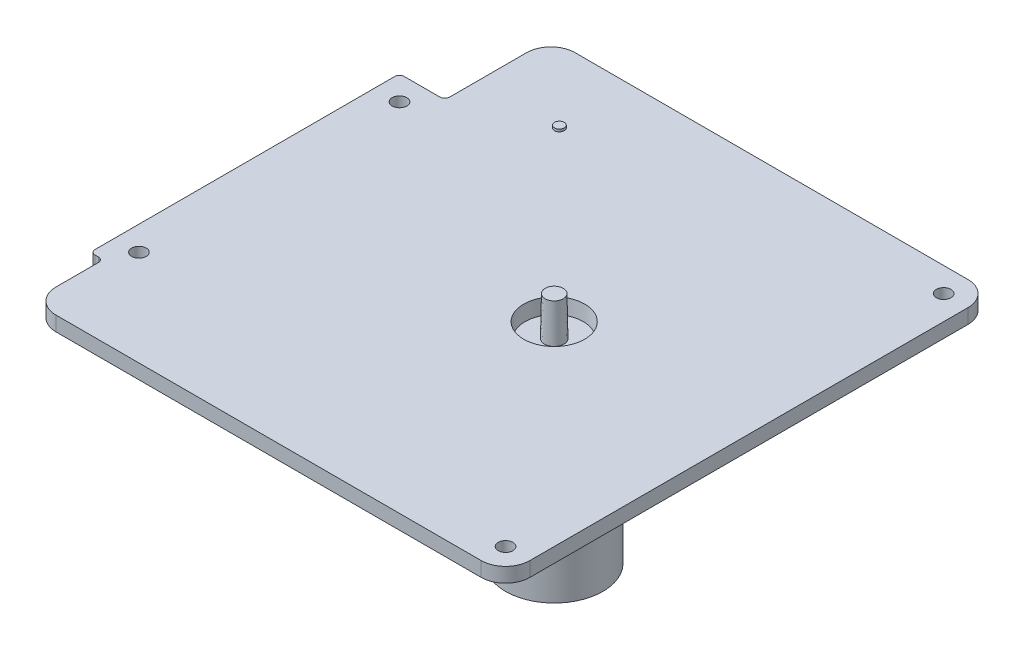
SolidWorks part; units mm, degrees
ref_plane "Front Plane" through (0, 0, 0) normal (0, 0, 1) x (1, 0, 0)
ref_plane "Top Plane" through (0, 0, 0) normal (0, 1, 0) x (1, 0, 0)
ref_plane "Right Plane" through (0, 0, 0) normal (1, 0, 0) x (0, 0, -1)
ref_plane "Plane1" through (0, 23, 0) normal (0, 1, 0) x (1, 0, 0)
sketch "Sketch1" plane through (0, 23, 0) normal (0, 1, 0) x (1, 0, 0)
  line L0 (98.3054, 50) -> (98.3054, 28.2195)
  line L1 (189, 50) -> (98.3054, 50)
  line L2 (189, 50) -> (189, -50)
  line L3 (189, -50) -> (97.6502, -50)
  line L5 (98.3054, 28.2195) -> (89, 28.2195)
  line L6 (89, 28.2195) -> (89, -35.308)
  line L7 (89, -35.308) -> (91.6598, -35.308)
  line L8 (91.6598, -35.308) -> (91.6598, -50)
  line L9 (91.6598, -50) -> (97.6502, -50)
  line L10 (94.8054, 33.2195) -> (98.3054, 33.2195) construction
  line L11 (184, 45) -> (184, 50) construction
  line L12 (93.3054, 31.7195) -> (93.3054, 28.2195) construction
  line L13 (99.4745, -35.308) -> (86.1225, -35.308) construction
  line L14 (88.1598, -40.308) -> (91.6598, -40.308) construction
  line L15 (86.6598, -38.808) -> (86.6598, -35.308) construction
  line L16 (189, 0) -> (190, 0) construction
  line L17 (190, -60) -> (190, 60) construction
  line L18 (105.0183, -40) -> (185.0183, -40) construction
  line L19 (105.0183, -40) -> (105.0183, 40) construction
  line L20 (105.0183, 40) -> (185.0183, 40) construction
  line L21 (185.0183, -40) -> (185.0183, 40) construction
  line L22 (184, 45) -> (189, 45) construction
  line L23 (184, -45) -> (189, -45) construction
  line L24 (184, -45) -> (184, -50) construction
  line L25 (94, 23.2195) -> (94, 28.2195) construction
  line L26 (94, 23.2195) -> (89, 23.2195) construction
  line L27 (94, -30.308) -> (94, -35.308) construction
  line L28 (94, -30.308) -> (89, -30.308) construction
  line L29 (190, -55) -> (190, 55) construction
  circle A0 centre (86.6598, -40.308) radius 1.5 construction
  circle A1 centre (93.3054, 33.2195) radius 1.5 construction
  circle A2 centre (184, 45) radius 1.5 construction
  circle A3 centre (184, 45) radius 1.5 construction
  circle A4 centre (184, -45) radius 1.5 construction
  circle A6 centre (94, 23.2195) radius 1.5 construction
  circle A7 centre (94, -30.308) radius 1.5 construction
  point P32 (185.0183, 0)
  dimension "D1" = 100
  dimension "D2" = 80
  dimension "D3" = 3.5
  dimension "D4" = 5
  dimension "D5" = 1
  dimension "D6" = 100
extrude "Boss-Extrude1" add sketch "Sketch1" along normal blind 3
fillet "Fillet3" radius 5 4 edges at (189, 24.5, -50) (98.3054, 24.5, -50) (91.6598, 24.5, 50) (189, 24.5, 50)
fillet "Fillet2" radius 1 4 edges at (89, 24.5, -28.2195) (98.3054, 24.5, -28.2195) (91.6598, 24.5, 35.308) (89, 24.5, 35.308)
sketch "Sketch2" plane through (0, 23, 0) normal (0, 1, 0) x (1, 0, 0)
  circle A0 centre (184, -45) radius 1.5 construction
  circle A1 centre (184, -45) radius 1.5
  circle A2 centre (94, -30.308) radius 1.5 construction
  circle A3 centre (94, -30.308) radius 1.5
  circle A4 centre (94, 23.2195) radius 1.5 construction
  circle A5 centre (94, 23.2195) radius 1.5
  circle A6 centre (184, 45) radius 1.5 construction
  circle A7 centre (184, 45) radius 1.5
extrude "Cut-Extrude1" cut sketch "Sketch2" along normal up to surface (3 mm away) up to face at (116.9913, 26, 1.7721)
sketch "Sketch5" plane through (0, 23, 0) normal (0, 1, 0) x (1, 0, 0)
  line L0 (189, 50) -> (189, -50) construction
  circle A0 centre (149, 0) radius 10
  circle A1 centre (149, 0) radius 6 construction
  circle A2 centre (149, 0) radius 2 construction
  circle A3 centre (149, 0) radius 33.75 construction
  circle A4 centre (115.0653, 35) radius 15 construction
  point P4 (189, 0)
  dimension "D2" = 20
  dimension "D3" = 12
  dimension "D4" = 4
  dimension "D5" = 67.5
  dimension "D6" = 30
  dimension "D1" = 40
  dimension "D7" = 35
extrude "Boss-Extrude2" add sketch "Sketch5" against normal blind 40
sketch "Sketch3" plane through (0, 23, 0) normal (0, 1, 0) x (1, 0, 0)
  line L0 (189, 50) -> (189, -50) construction
  circle A0 centre (149, 0) radius 6
  circle A1 centre (149, 0) radius 6 construction
  point P6 (189, 0)
extrude "Cut-Extrude3" cut sketch "Sketch3" along normal blind 3 draft 5 draft outward yes
sketch "Sketch6" plane through (0, 23, 0) normal (0, 1, 0) x (1, 0, 0)
  circle A0 centre (149, 0) radius 2
  circle A1 centre (149, 0) radius 2 construction
extrude "Boss-Extrude3" add sketch "Sketch6" along normal blind 8 draft 1
sketch "Sketch7" plane through (0, 26, 0) normal (0, 1, 0) x (1, 0, 0)
  circle A0 centre (115.0653, 35) radius 1
  dimension "D1" = 2
extrude "Boss-Extrude4" add sketch "Sketch7" along normal blind 0.5
